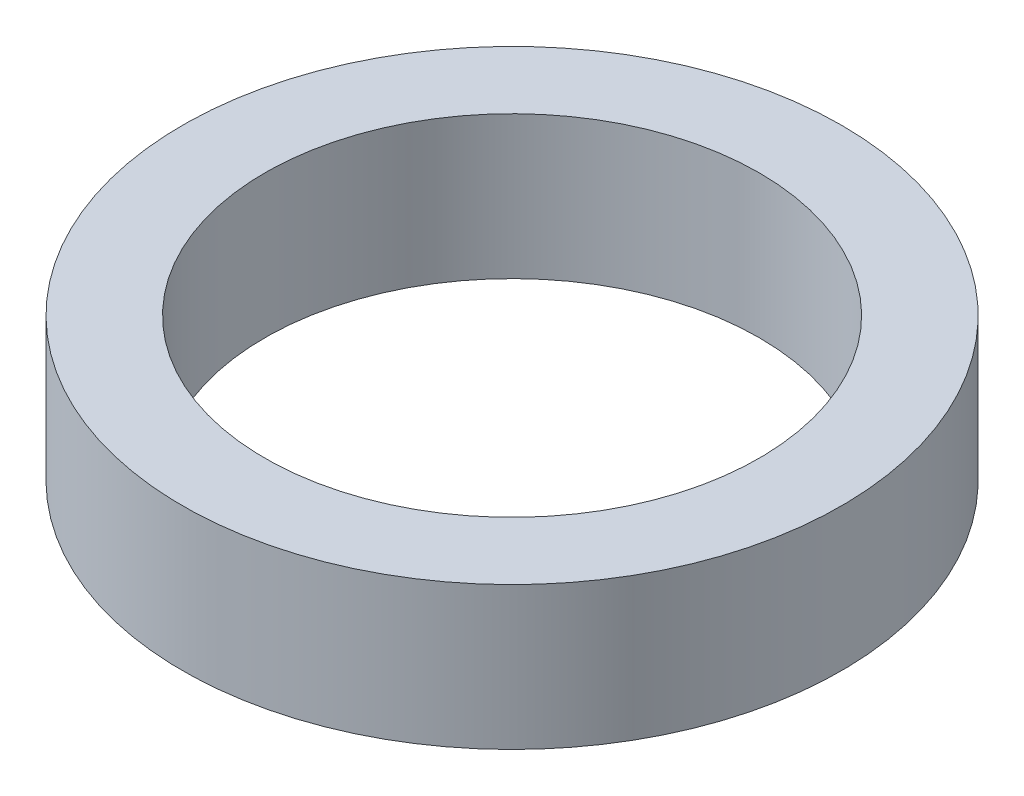
SolidWorks part; units mm, degrees
ref_plane "Front Plane" through (0, 0, 0) normal (0, 0, 1) x (1, 0, 0)
ref_plane "Top Plane" through (0, 0, 0) normal (0, 1, 0) x (1, 0, 0)
ref_plane "Right Plane" through (0, 0, 0) normal (1, 0, 0) x (0, 0, -1)
sketch "Sketch1" plane through (0, 0, 0) normal (0, 1, 0) x (1, 0, 0)
  circle A0 centre (0, 0) radius 30
  dimension "FLANGE_OD" = 60
extrude "Boss-Extrude1" add sketch "Sketch1" along normal blind 13
sketch "Sketch2" plane through (0, 0, 0) normal (0, 1, 0) x (1, 0, 0)
  circle A0 centre (0, 0) radius 22.5
  dimension "BORE_D" = 45
extrude "Cut-Extrude1" cut sketch "Sketch2" along normal through all
sketch "Sketch3" plane through (0, 13, 0) normal (0, 1, 0) x (1, 0, 0)
  circle A0 centre (0, 0) radius 13.4774 construction
  circle A1 centre (-13.4774, 0) radius 1.5
  dimension "BOLT_D" = 3
  dimension "BOLT_PCD" = 26.9548
extrude "Cut-Extrude2" cut sketch "Sketch3" against normal blind 8.5109 rebuild error yes
pattern_circular "CirPattern1" count 5 over 360 rebuild error yes
